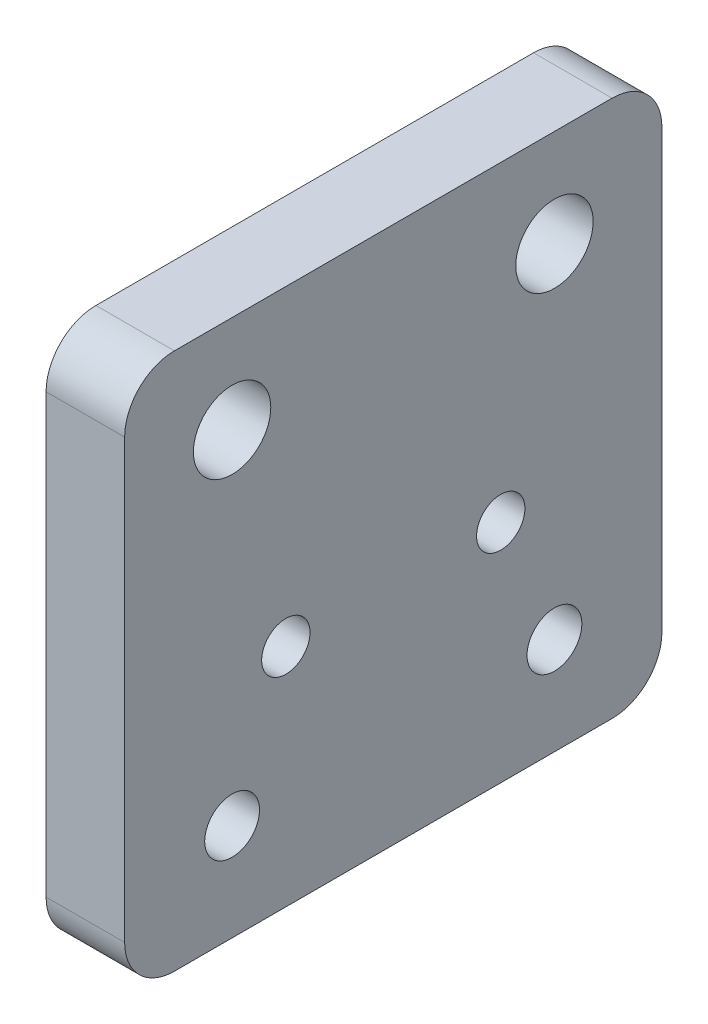
SolidWorks part; units mm, degrees
ref_plane "Front" through (0, 0, 0) normal (0, 0, 1) x (1, 0, 0)
ref_plane "Top" through (0, 0, 0) normal (0, 1, 0) x (1, 0, 0)
ref_plane "Right" through (0, 0, 0) normal (1, 0, 0) x (0, 0, -1)
sketch "Sketch2" plane through (0, 0, 0) normal (1, 0, 0) x (0, 0, -1)
  line L1 (-25, -25) -> (25, -25)
  line L2 (-25, -25) -> (-25, 25)
  line L3 (-25, 25) -> (25, 25)
  line L4 (25, -25) -> (25, 25)
  line L5 (0, 25) -> (0, -25) construction
  line L6 (-25, 0) -> (25, 0) construction
  point P0 (0, 0)
  dimension "D1" = 50
  dimension "D2" = 50
extrude "Boss-Extrude1" add sketch "Sketch2" along normal blind 7.31
sketch "Sketch6" plane through (0, 0, 0) normal (1, 0, 0) x (0, 0, -1)
  line L1 (15, -15.95) -> (-15, -15.95) construction
  line L2 (15, -15.95) -> (15, 15.95) construction
  line L3 (15, 15.95) -> (-15, 15.95) construction
  line L4 (-15, -15.95) -> (-15, 15.95) construction
  line L5 (0, 15.95) -> (0, -15.95) construction
  line L6 (15, 0) -> (-15, 0) construction
  circle A0 centre (-15, 15.95) radius 3.6
  circle A1 centre (15, 15.95) radius 3.6
  circle A2 centre (-15, -15.95) radius 2.55
  circle A3 centre (15, -15.95) radius 2.55
  point P0 (0, 0)
  dimension "D3" = 7.2
  dimension "D4" = 5.1
  dimension "D1" = 31.9
  dimension "D2" = 30
extrude "Cut-Extrude2" cut sketch "Sketch6" along normal through all
sketch "Sketch7" plane through (0, 0, 0) normal (-1, 0, 0) x (0, 0, 1)
  circle A0 centre (-15, -15.95) radius 5.05
  circle A1 centre (15, -15.95) radius 5.05
  circle A2 centre (-15, 15.95) radius 6
  circle A3 centre (15, 15.95) radius 6
  dimension "D1" = 12
  dimension "D2" = 10.1
extrude "Cut-Extrude3" cut sketch "Sketch7" against normal blind 2
hole_wizard "M4 Clearance Hole1" positions "Sketch11" profile "Sketch12" hole size "M4" standard "ANSI Metric" end condition through all
sketch "Sketch11" plane through (7.31, 0, 0) normal (1, 0, 0) x (0, 0, -1)
  line L2 (-10, -4) -> (10, -4) construction
  line L5 (0, 0) -> (0, -4) construction
  point P0 (-10, -4)
  point P2 (10, -4)
  dimension "D1" = 20
  dimension "D2" = 4
sketch "Sketch12" plane through (7.31, -4, 10) normal (0, 1, 0) x (0, 0, -1)
  line L0 (0, 0) -> (0, 7.31)
  line L1 (0, 7.31) -> (2.25, 7.31)
  line L2 (2.25, 7.31) -> (2.25, 0)
  line L5 (2.25, 0) -> (0, 0)
  line L11 (0, -6.35) -> (0, 107.95) construction
  dimension "Thru Hole Dia." = 4.5
  dimension "Thru Hole Depth" = 7.31
fillet "Fillet1" radius 4.635 4 edges at (3.655, -25, -25) (3.655, -25, 25) (3.655, 25, -25) (3.655, 25, 25)
